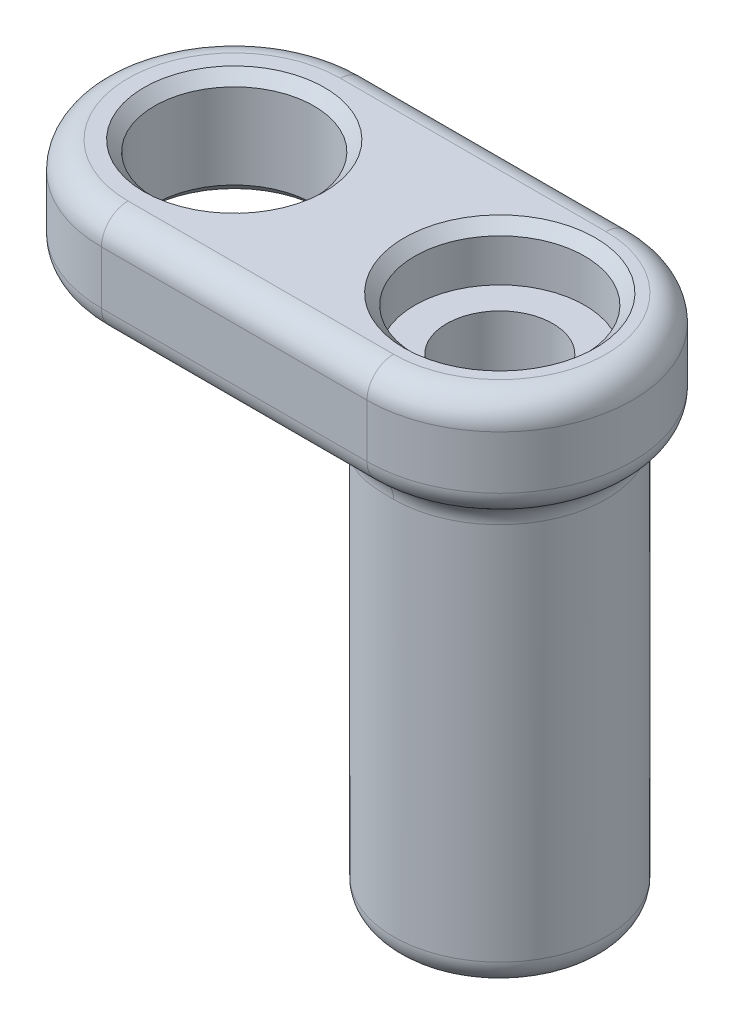
SolidWorks part; units mm, degrees
ref_plane "Front Plane" through (0, 0, 0) normal (0, 0, 1) x (1, 0, 0)
ref_plane "Top Plane" through (0, 0, 0) normal (0, 1, 0) x (1, 0, 0)
ref_plane "Right Plane" through (0, 0, 0) normal (1, 0, 0) x (0, 0, -1)
sketch "Sketch2" plane through (0, 0, 0) normal (0, 1, 0) x (1, 0, 0)
  line L0 (-28.3146, 0) -> (21.6854, 0) construction
  line L1 (-28.3146, 25) -> (21.6854, 25)
  line L2 (-28.3146, -25) -> (21.6854, -25)
  arc A0 (-28.3146, 25) -> (-28.3146, -25) centre (-28.3146, 0) ccw
  arc A1 (21.6854, -25) -> (21.6854, 25) centre (21.6854, 0) ccw
  point P3 (-3.3146, 0)
  dimension "D2" = 25
  dimension "D1" = 50
extrude "Boss-Extrude1" add sketch "Sketch2" along normal blind 20
fillet "Fillet1" radius 5 8 edges at (-3.3146, 20, -25) (46.6854, 20, 0) (-3.3146, 20, 25) (-53.3146, 20, 0) (-3.3146, 0, 25) (46.6854, 0, 0) (-3.3146, 0, -25) (-53.3146, 0, 0)
sketch "Sketch5" plane through (0, 20, 0) normal (0, 1, 0) x (1, 0, 0)
  circle A0 centre (-28.3146, 0) radius 15
  point P0 (-28.3146, 0)
  point P3 (-28.3146, 0)
  dimension "D1" = 30
extrude "Cut-Extrude1" cut sketch "Sketch5" against normal blind 20
chamfer "Chamfer1" distance 2 angle 45 2 edges at (-28.3146, 0, 15) (-28.3146, 20, 15)
sketch "Sketch7" plane through (0, 0, 0) normal (0, -1, 0) x (1, 0, 0)
  circle A0 centre (21.6854, 0) radius 20
  dimension "D1" = 40
extrude "Boss-Extrude2" add sketch "Sketch7" along normal blind 80
sketch "Sketch9" plane through (0, 20, 0) normal (0, 1, 0) x (1, 0, 0)
  point P0 (21.6854, 0)
  point P3 (21.6854, 0)
hole_wizard "CBORE for M10 Hex Head Bolt2" positions "Sketch9" profile "Sketch10" counterbore size "M10" standard "ANSI Metric" end condition through all
sketch "Sketch10" plane through (21.6854, 20, 0) normal (1, 0, 0) x (0, 0, 1)
  line L0 (0, 0) -> (0, 100)
  line L1 (0, 100) -> (10, 100)
  line L3 (10, 100) -> (10, 10)
  line L4 (10, 10) -> (16, 10)
  line L5 (16, 10) -> (16, 0)
  line L7 (16, 0) -> (0, 0)
  line L11 (0, -6.35) -> (0, 107.95) construction
  dimension "Thru Hole Dia." = 20
  dimension "Thru Hole Depth" = 100
  dimension "C'Bore Dia." = 32
  dimension "C'Bore Depth" = 10
chamfer "Chamfer2" distance 2 angle 45 1 edges at (21.6854, 20, 16)
fillet "Fillet2" radius 5 1 edges at (21.6854, -80, -20)
fillet "Fillet3" radius 5 2 edges at (41.6854, 0, 0) (1.6854, 0, 0)
